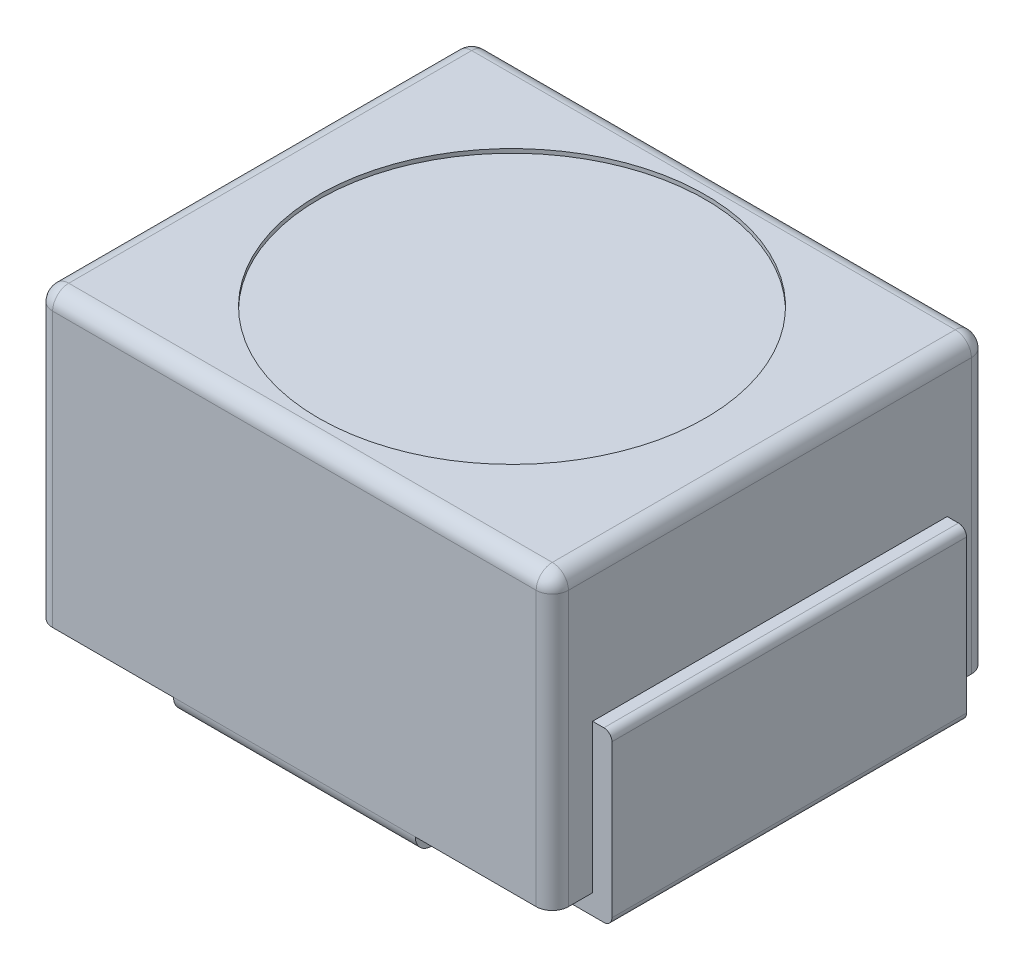
SolidWorks part; units mm, degrees
ref_plane "Спереди" through (0, 0, 0) normal (0, 0, 1) x (1, 0, 0)
ref_plane "Сверху" through (0, 0, 0) normal (0, 1, 0) x (1, 0, 0)
ref_plane "Справа" through (0, 0, 0) normal (1, 0, 0) x (0, 0, -1)
sketch "Эскиз2" plane through (0, 0, 0) normal (0, 1, 0) x (1, 0, 0)
  line L1 (-1.6, 1.35) -> (1.6, 1.35)
  line L2 (-1.6, 1.35) -> (-1.6, -1.35)
  line L3 (-1.6, -1.35) -> (1.6, -1.35)
  line L4 (1.6, 1.35) -> (1.6, -1.35)
  line L5 (-1.6, 1.35) -> (1.6, -1.35) construction
  line L6 (-1.6, -1.35) -> (1.6, 1.35) construction
  point P0 (0, 0)
  dimension "D1" = 3.2
  dimension "D2" = 2.7
extrude "Бобышка-Вытянуть1" add sketch "Эскиз2" along normal blind 1.9
fillet "Скругление1" radius 0.1 4 edges at (0, 1.9, 1.35) (-1.6, 1.9, 0) (0, 1.9, -1.35) (1.6, 1.9, 0)
fillet "Скругление2" radius 0.1 5 edges at (-1.5707, 1.8707, 1.3207) (1.5707, 1.8707, 1.3207) (0, 0, 1.35) (-1.6, 0.9, 1.35) (1.6, 0.9, 1.35)
fillet "Скругление3" radius 0.1 4 edges at (1.5707, 1.8707, -1.3207) (1.5707, 0.0293, 1.3207) (1.6, 0.9, -1.35) (1.6, 0, -0.05)
fillet "Скругление4" radius 0.1 4 edges at (-1.5707, 1.8707, -1.3207) (1.5707, 0.0293, -1.3207) (-1.6, 0.9, -1.35) (-0.05, 0, -1.35)
fillet "Скругление5" radius 0.1 3 edges at (-1.5707, 0.0293, -1.3207) (-1.5707, 0.0293, 1.3207) (-1.6, 0, 0)
sketch "Эскиз3" plane through (0, 1.9, 0) normal (0, 1, 0) x (1, 0, 0)
  circle A0 centre (0, 0) radius 1.2
extrude "Вырез-Вытянуть1" cut sketch "Эскиз3" against normal blind 0.025
sketch "Эскиз4" plane through (0, 0, 0) normal (0, -1, 0) x (1, 0, 0)
  line L0 (0, 0) -> (0, 0.1364) construction
  line L1 (0, 2.8279) -> (0, -2.2605) construction
  line L2 (0.75, -1.4164) -> (1.6778, -1.4164)
  line L3 (0.75, -1.4164) -> (0.75, 1.4195)
  line L4 (0.75, 1.4195) -> (1.6778, 1.4195)
  line L5 (1.6778, -1.4164) -> (1.6778, 1.4195)
  line L6 (-0.75, -1.4164) -> (-0.75, 1.4195)
  line L7 (-0.75, 1.4195) -> (-1.6778, 1.4195)
  line L8 (-1.6778, -1.4164) -> (-1.6778, 1.4195)
  line L9 (-0.75, -1.4164) -> (-1.6778, -1.4164)
extrude "Вырез-Вытянуть2" cut sketch "Эскиз4" against normal blind 0.1
ref_plane "Плоскость1" through (0, 0, 0) normal (0, 0, -1) x (-1, 0, 0)
sketch "Эскиз6" plane through (0, 0, 0) normal (0, 0, -1) x (-1, 0, 0)
  line L0 (1.6, 0.1) -> (0.8706, 0.1)
  line L1 (1.5, 0.1) -> (0.75, 0.1) construction
  line L2 (0.8706, 0.1) -> (0.8706, 0.0254)
  line L3 (0.9206, -0.0246) -> (1.67, -0.0246)
  line L4 (1.6, 0.1) -> (1.6, 1.0213)
  line L5 (1.6, 1.8) -> (1.6, 0.1) construction
  line L6 (1.6, 1.0213) -> (1.67, 1.0213)
  line L7 (1.72, 0.9713) -> (1.72, 0.0254)
  line L8 (0, 0) -> (0, 0.9713) construction
  line L9 (-1.6, 1.0213) -> (-1.67, 1.0213)
  line L10 (-1.6, 0.1) -> (-1.6, 1.0213)
  line L11 (-1.6, 0.1) -> (-0.8706, 0.1)
  line L12 (-0.8706, 0.1) -> (-0.8706, 0.0254)
  line L13 (-0.9206, -0.0246) -> (-1.67, -0.0246)
  line L14 (-1.72, 0.9713) -> (-1.72, 0.0254)
  arc A0 (1.72, 0.9713) -> (1.67, 1.0213) centre (1.67, 0.9713) ccw
  arc A1 (1.72, 0.0254) -> (1.67, -0.0246) centre (1.67, 0.0254) cw
  arc A2 (0.8706, 0.0254) -> (0.9206, -0.0246) centre (0.9206, 0.0254) ccw
  arc A3 (-1.72, 0.9713) -> (-1.67, 1.0213) centre (-1.67, 0.9713) cw
  arc A4 (-0.8706, 0.0254) -> (-0.9206, -0.0246) centre (-0.9206, 0.0254) cw
  arc A5 (-1.72, 0.0254) -> (-1.67, -0.0246) centre (-1.67, 0.0254) ccw
  dimension "D1" = 0.05
extrude "Бобышка-Вытянуть3" add sketch "Эскиз6" along normal mid plane 2.2
